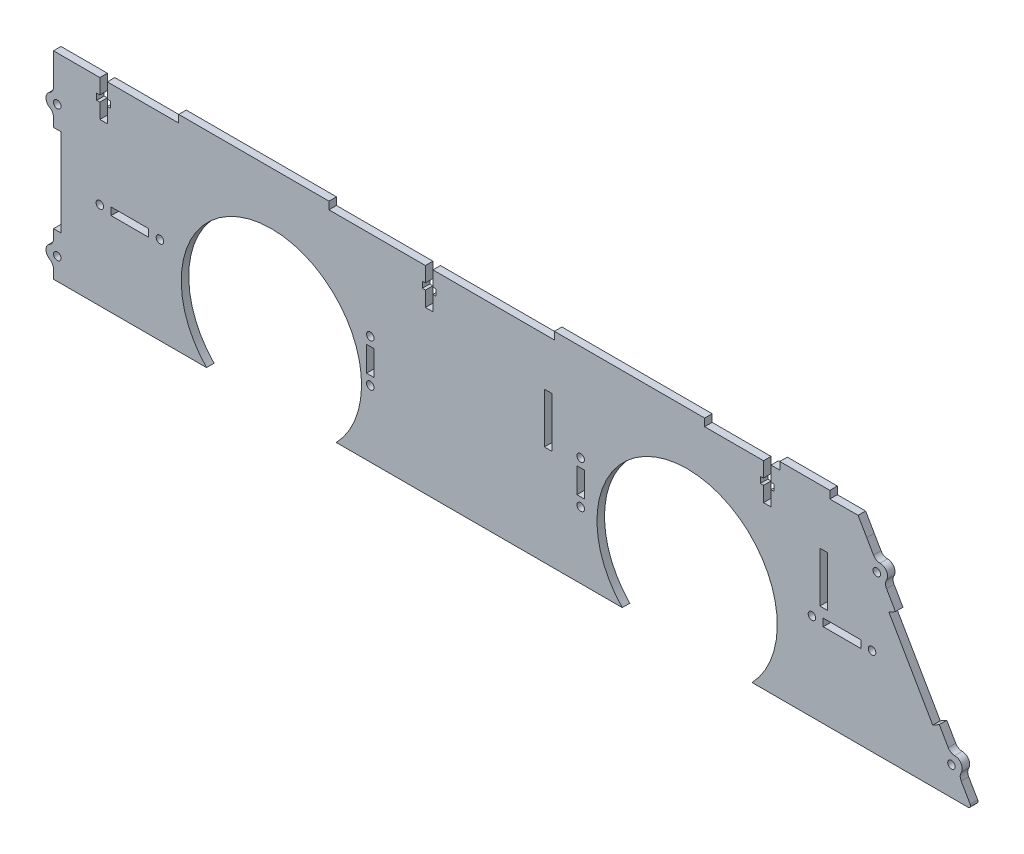
SolidWorks part; units mm, degrees
ref_plane "Спереди" through (0, 0, 0) normal (0, 0, 1) x (1, 0, 0)
ref_plane "Сверху" through (0, 0, 0) normal (0, 1, 0) x (1, 0, 0)
ref_plane "Справа" through (0, 0, 0) normal (1, 0, 0) x (0, 0, -1)
sketch "Эскиз1" plane through (0, 0, 0) normal (0, 0, 1) x (1, 0, 0)
  line L5 (-42.1466, 73) -> (0, 0)
  line L6 (-366.8766, 73) -> (-42.1466, 73)
  line L7 (-366.8766, 0) -> (-366.8766, 73)
  line L8 (0, 0) -> (-366.8766, 0)
  dimension "D1" = 60
  dimension "D2" = 73
  dimension "D3" = 324.73
  dimension "D4" = 84.2931
extrude "Бобышка-Вытянуть1" add sketch "Эскиз1" along normal blind 3
sketch "Эскиз2" plane through (0, 0, 3) normal (0, 0, 1) x (1, 0, 0)
  line L0 (-366.8766, 73) -> (-366.8766, 0) construction
  line L1 (-366.8766, 52.5) -> (-363.8766, 52.5)
  line L2 (-366.8766, 52.5) -> (-366.8766, 17.5)
  line L3 (-366.8766, 17.5) -> (-363.8766, 17.5)
  line L4 (-363.8766, 52.5) -> (-363.8766, 17.5)
  point P6 (-366.8766, 35)
  dimension "D1" = 35
  dimension "D2" = 3
  dimension "D3" = 35
extrude "Вырез-Вытянуть1" cut sketch "Эскиз2" against normal blind 3
sketch "Эскиз3" plane through (0, 0, 3) normal (0, 0, 1) x (1, 0, 0)
  line L0 (-33.2874, 51.6554) -> (-30.6893, 53.1554)
  line L1 (-33.2874, 51.6554) -> (-15.7874, 21.3446)
  line L2 (-30.6893, 53.1554) -> (-13.1893, 22.8446)
  line L3 (-15.7874, 21.3446) -> (-13.1893, 22.8446)
  line L4 (-45.6107, 73) -> (-3.4641, 0) construction
  line L5 (-42.1466, 73) -> (-366.8766, 73) construction
  line L9 (0, 0) -> (-42.1466, 73) construction
  line L10 (-366.8766, 0) -> (0, 0) construction
  line L11 (0, 0) -> (-42.1466, 73) construction
  point P12 (-24.5374, 36.5)
  point P13 (-24.5374, 36.5)
  dimension "D1" = 35
  dimension "D2" = 3
extrude "Вырез-Вытянуть2" cut sketch "Эскиз3" against normal blind 3
sketch "Эскиз4" plane through (0, 0, 3) normal (0, 0, 1) x (1, 0, 0)
  line L0 (-366.8766, 0) -> (0, 0) construction
  line L1 (-241.8766, 40) -> (-238.8766, 40)
  line L2 (-241.8766, 40) -> (-241.8766, 30)
  line L3 (-241.8766, 30) -> (-238.8766, 30)
  line L4 (-238.8766, 40) -> (-238.8766, 30)
  line L5 (-241.8766, 40) -> (-238.8766, 30) construction
  line L6 (-241.8766, 30) -> (-238.8766, 40) construction
  line L7 (-157.8766, 40) -> (-154.8766, 40)
  line L8 (-157.8766, 40) -> (-157.8766, 30)
  line L9 (-157.8766, 30) -> (-154.8766, 30)
  line L10 (-154.8766, 40) -> (-154.8766, 30)
  line L11 (-157.8766, 40) -> (-154.8766, 30) construction
  line L12 (-157.8766, 30) -> (-154.8766, 40) construction
  point P0 (-240.3766, 35)
  point P5 (-156.3766, 35)
  dimension "D1" = 3
  dimension "D2" = 10
  dimension "D3" = 84
  dimension "D4" = 123.5
  dimension "D5" = 35
extrude "Вырез-Вытянуть3" cut sketch "Эскиз4" against normal blind 3
sketch "Эскиз5" plane through (0, 0, 3) normal (0, 0, 1) x (1, 0, 0)
  line L1 (-343.8766, 36.5) -> (-328.8766, 36.5)
  line L2 (-343.8766, 36.5) -> (-343.8766, 33.5)
  line L3 (-343.8766, 33.5) -> (-328.8766, 33.5)
  line L4 (-328.8766, 36.5) -> (-328.8766, 33.5)
  line L5 (-343.8766, 36.5) -> (-328.8766, 33.5) construction
  line L6 (-343.8766, 33.5) -> (-328.8766, 36.5) construction
  line L7 (-59.5366, 36.5) -> (-44.5366, 36.5)
  line L8 (-59.5366, 36.5) -> (-59.5366, 33.5)
  line L9 (-59.5366, 33.5) -> (-44.5366, 33.5)
  line L10 (-44.5366, 36.5) -> (-44.5366, 33.5)
  line L11 (-59.5366, 36.5) -> (-44.5366, 33.5) construction
  line L12 (-59.5366, 33.5) -> (-44.5366, 36.5) construction
  point P0 (-336.3766, 35)
  point P5 (-52.0366, 35)
  dimension "D1" = 15
  dimension "D2" = 3
  dimension "D3" = 27.5
  dimension "D4" = 284.34
  dimension "D5" = 35
extrude "Вырез-Вытянуть4" cut sketch "Эскиз5" against normal blind 3
sketch "Эскиз6" plane through (0, 73, 0) normal (0, 1, 0) x (1, 0, 0)
  line L0 (-42.1466, -3) -> (-366.8766, -3) construction
  line L1 (-366.8766, 0) -> (-42.1466, 0)
  line L2 (-366.8766, 0) -> (-366.8766, -3)
  line L3 (-366.8766, -3) -> (-42.1466, -3)
  line L4 (-42.1466, 0) -> (-42.1466, -3)
extrude "Бобышка-Вытянуть2" add sketch "Эскиз6" along normal blind 6
sketch "Эскиз7" plane through (0, 0, 3) normal (0, 0, 1) x (1, 0, 0)
  line L0 (-366.8766, 17.5) -> (-366.8766, 0) construction
  line L1 (-363.8766, 35) -> (-385.1167, 35) construction
  line L2 (-363.8766, 17.5) -> (-363.8766, 52.5) construction
  circle A0 centre (-365.3766, 8.75) radius 1.5
  circle A1 centre (-365.3766, 61.25) radius 1.5
  point P5 (-366.8766, 8.75)
  dimension "D1" = 3
  dimension "D2" = 1.5
sketch "Эскиз8" plane through (-366.8766, 0, 0) normal (-1, 0, 0) x (0, 0, 1)
  line L0 (0, 17.5) -> (0, 0) construction
  line L1 (0, 8.75) -> (3, 8.75)
  line L2 (0, 8.75) -> (0, 5.75)
  line L3 (0, 5.75) -> (3, 5.75)
  line L4 (3, 8.75) -> (3, 5.75)
  line L5 (3, 17.5) -> (3, 0) construction
  dimension "D1" = 3
revolve "Повернуть1" add sketch "Эскиз8" angle 360 about L1
sketch "Эскиз9" plane through (-366.8766, 0, 0) normal (-1, 0, 0) x (0, 0, 1)
  line L0 (0, 79) -> (0, 52.5) construction
  line L1 (0, 61.25) -> (3, 61.25)
  line L2 (0, 61.25) -> (0, 58.25)
  line L3 (0, 58.25) -> (3, 58.25)
  line L4 (3, 61.25) -> (3, 58.25)
  line L5 (3, 79) -> (3, 52.5) construction
  dimension "D1" = 3
  dimension "D2" = 8.75
revolve "Повернуть2" add sketch "Эскиз9" angle 360 about L1
extrude "Вырез-Вытянуть6" cut sketch "Эскиз7" against normal blind 3
fillet "Скругление1" radius 3 4 edges at (-366.8766, 11.75, 1.5) (-366.8766, 5.75, 1.5) (-366.8766, 58.25, 1.5) (-366.8766, 64.25, 1.5)
sketch "Эскиз14" plane through (0, 0, 3) normal (0, 0, 1) x (1, 0, 0)
  line L0 (-154.8766, 40) -> (-157.8766, 40) construction
  line L1 (-157.8766, 30) -> (-154.8766, 30) construction
  line L2 (-241.8766, 30) -> (-238.8766, 30) construction
  circle A0 centre (-156.3766, 43.5) radius 1.5
  circle A1 centre (-156.3766, 26.5) radius 1.5
  circle A2 centre (-240.3766, 26.5) radius 1.5
  circle A3 centre (-240.3766, 43.5) radius 1.5
  point P11 (-156.3766, 40)
  point P20 (-240.3766, 30)
  dimension "D1" = 3
  dimension "D2" = 3.5
  dimension "D3" = 3.5
extrude "Вырез-Вытянуть9" cut sketch "Эскиз14" against normal blind 3
sketch "Эскиз15" plane through (0, 0, 3) normal (0, 0, 1) x (1, 0, 0)
  line L0 (-59.5366, 36.5) -> (-59.5366, 33.5) construction
  line L1 (-44.5366, 33.5) -> (-44.5366, 36.5) construction
  line L2 (-343.8766, 36.5) -> (-343.8766, 33.5) construction
  line L3 (-328.8766, 33.5) -> (-328.8766, 36.5) construction
  circle A0 centre (-324.3766, 35) radius 1.5
  circle A1 centre (-348.3766, 35) radius 1.5
  circle A2 centre (-64.0366, 35) radius 1.5
  circle A3 centre (-40.0366, 35) radius 1.5
  point P16 (-59.5366, 35)
  dimension "D1" = 3
  dimension "D2" = 4.5
  dimension "D3" = 4.5
  dimension "D4" = 4.5
  dimension "D5" = 4.5
extrude "Вырез-Вытянуть10" cut sketch "Эскиз15" against normal blind 3
sketch "Эскиз16" plane through (0, 0, 0) normal (0.866, 0.5, 0) x (0, 0, -1)
  line L0 (-3, 0) -> (-3, 26.3786) construction
  line L1 (-3, 11.0586) -> (0, 11.0586)
  line L2 (-3, 11.0586) -> (-3, 14.0586)
  line L3 (-3, 14.0586) -> (0, 14.0586)
  line L4 (0, 11.0586) -> (0, 14.0586)
  line L5 (0, 0) -> (0, 26.3786) construction
  dimension "D1" = 3
  dimension "D2" = 12.32
revolve "Повернуть3" add sketch "Эскиз16" angle 360 about L3
sketch "Эскиз17" plane through (0, 0, 0) normal (0.866, 0.5, 0) x (0, 0, -1)
  line L0 (-3, 61.3786) -> (-3, 84.2931) construction
  line L1 (-3, 73.6986) -> (0, 73.6986)
  line L2 (-3, 73.6986) -> (-3, 76.6986)
  line L3 (-3, 76.6986) -> (0, 76.6986)
  line L4 (0, 73.6986) -> (0, 76.6986)
  line L5 (0, 61.3786) -> (0, 84.2931) construction
  dimension "D1" = 3
  dimension "D2" = 12.32
revolve "Повернуть4" add sketch "Эскиз17" angle 360 about L1
sketch "Эскиз18" plane through (0, 0, 3) normal (0, 0, 1) x (1, 0, 0)
  line L1 (-15.7874, 21.3446) -> (-3.4641, 0) construction
  line L2 (0, 0) -> (-5.5293, 9.577) construction
  line L3 (-366.8766, 0) -> (0, 0) construction
  line L5 (-9.6257, 10.6723) -> (-6.0018, 12.7646) construction
  circle A0 centre (-38.15, 63.0777) radius 1.5
  circle A1 centre (-8.3267, 11.4223) radius 1.5
  dimension "D1" = 3
  dimension "D2" = 3
  dimension "D3" = 9.9223
  dimension "D4" = 1.5
  dimension "D5" = 7.4607
extrude "Вырез-Вытянуть11" cut sketch "Эскиз18" against normal blind 3
fillet "Скругление2" radius 3 4 edges at (-38.3493, 66.423, 1.5) (-35.3493, 61.2268, 1.5) (-8.5293, 14.7732, 1.5) (-5.5293, 9.577, 1.5)
chamfer "Фаска1" distance 6 angle 30 1 edges at (-42.1466, 79, 1.5) first distance on face at (-42.1466, 76, 1.5)
sketch "Эскиз19" plane through (0, 0, 3) normal (0, 0, 1) x (1, 0, 0)
  line L0 (-366.8766, 0) -> (0, 0) construction
  line L1 (-363.8766, 17.5) -> (-363.8766, 52.5) construction
  circle A0 centre (-279.8766, 25) radius 36
  circle A1 centre (-113.8766, 25) radius 36
  dimension "D4" = 72
  dimension "D1" = 25
  dimension "D2" = 166
  dimension "D3" = 84
extrude "Вырез-Вытянуть12" cut sketch "Эскиз19" against normal blind 3
sketch "Эскиз24" plane through (0, 79, 0) normal (0, 1, 0) x (1, 0, 0)
  line L0 (-366.8766, -3) -> (-45.6107, -3) construction
  line L1 (-56.8766, -3) -> (-76.8766, -3)
  line L2 (-56.8766, -3) -> (-56.8766, 0)
  line L3 (-56.8766, 0) -> (-76.8766, 0)
  line L4 (-76.8766, -3) -> (-76.8766, 0)
  line L5 (-45.6107, 0) -> (-366.8766, 0) construction
  line L7 (-106.8766, -3) -> (-166.8766, -3)
  line L8 (-106.8766, -3) -> (-106.8766, 0)
  line L9 (-106.8766, 0) -> (-166.8766, 0)
  line L10 (-166.8766, -3) -> (-166.8766, 0)
  line L11 (-316.8766, -3) -> (-256.8766, -3)
  line L12 (-316.8766, -3) -> (-316.8766, 0)
  line L13 (-316.8766, 0) -> (-256.8766, 0)
  line L14 (-256.8766, -3) -> (-256.8766, 0)
  dimension "D1" = 50
  dimension "D2" = 60
  dimension "D3" = 60
  dimension "D4" = 200
  dimension "D5" = 20
  dimension "D6" = 290
extrude "Бобышка-Вытянуть3" add sketch "Эскиз24" along normal blind 3
sketch "Эскиз25" plane through (0, 0, 3) normal (0, 0, 1) x (1, 0, 0)
  line L0 (-348.3766, 79) -> (-348.3766, 73)
  line L1 (-348.3766, 73) -> (-349.6266, 73)
  line L2 (-349.6266, 73) -> (-349.6266, 70.5)
  line L3 (-349.6266, 70.5) -> (-348.3766, 70.5)
  line L4 (-348.3766, 70.5) -> (-348.3766, 64.5)
  line L5 (-348.3766, 64.5) -> (-345.3766, 64.5)
  line L6 (-345.3766, 64.5) -> (-345.3766, 70.5)
  line L7 (-345.3766, 70.5) -> (-344.1266, 70.5)
  line L8 (-344.1266, 70.5) -> (-344.1266, 73)
  line L9 (-344.1266, 73) -> (-345.3766, 73)
  line L10 (-345.3766, 73) -> (-345.3766, 79)
  line L11 (-345.3766, 79) -> (-348.3766, 79)
  line L12 (-218.3766, 79) -> (-218.3766, 73)
  line L13 (-218.3766, 73) -> (-219.6266, 73)
  line L14 (-219.6266, 73) -> (-219.6266, 70.5)
  line L15 (-219.6266, 70.5) -> (-218.3766, 70.5)
  line L16 (-218.3766, 70.5) -> (-218.3766, 64.5)
  line L17 (-218.3766, 64.5) -> (-215.3766, 64.5)
  line L18 (-215.3766, 64.5) -> (-215.3766, 70.5)
  line L19 (-215.3766, 70.5) -> (-214.1266, 70.5)
  line L20 (-214.1266, 70.5) -> (-214.1266, 73)
  line L21 (-214.1266, 73) -> (-215.3766, 73)
  line L22 (-215.3766, 73) -> (-215.3766, 79)
  line L23 (-215.3766, 79) -> (-218.3766, 79)
  line L24 (-83.3766, 79) -> (-83.3766, 73)
  line L25 (-83.3766, 73) -> (-84.6266, 73)
  line L26 (-84.6266, 73) -> (-84.6266, 70.5)
  line L27 (-84.6266, 70.5) -> (-83.3766, 70.5)
  line L28 (-83.3766, 70.5) -> (-83.3766, 64.5)
  line L29 (-83.3766, 64.5) -> (-80.3766, 64.5)
  line L30 (-80.3766, 64.5) -> (-80.3766, 70.5)
  line L31 (-80.3766, 70.5) -> (-79.1266, 70.5)
  line L32 (-79.1266, 70.5) -> (-79.1266, 73)
  line L33 (-79.1266, 73) -> (-80.3766, 73)
  line L34 (-80.3766, 73) -> (-80.3766, 79)
  line L35 (-80.3766, 79) -> (-83.3766, 79)
  line L36 (-366.8766, 79) -> (-316.8766, 79) construction
  line L37 (-256.8766, 79) -> (-166.8766, 79) construction
  line L38 (-106.8766, 79) -> (-76.8766, 79) construction
  point P42 (-346.8766, 79)
  point P47 (-216.8766, 79)
  point P54 (-81.8766, 79)
  dimension "D1" = 6
  dimension "D2" = 3
  dimension "D3" = 2.5
  dimension "D4" = 5.5
  dimension "D5" = 6
  dimension "D6" = 3
  dimension "D7" = 2.5
  dimension "D8" = 5.5
  dimension "D9" = 6
  dimension "D10" = 3
  dimension "D11" = 2.5
  dimension "D12" = 5.5
  dimension "D13" = 20
  dimension "D14" = 150
  dimension "D15" = 285
extrude "Вырез-Вытянуть13" cut sketch "Эскиз25" against normal blind 3
fillet "Скругление3" radius 1 1 edges at (0, 0, 1.5)
sketch "Эскиз26" plane through (0, 0, 3) normal (0, 0, 1) x (1, 0, 0)
  line L0 (-253.9729, 0) -> (-139.7802, 0) construction
  line L1 (-170.8766, 60) -> (-167.8766, 60)
  line L2 (-170.8766, 60) -> (-170.8766, 40)
  line L3 (-170.8766, 40) -> (-167.8766, 40)
  line L4 (-167.8766, 60) -> (-167.8766, 40)
  line L5 (-60.8766, 60) -> (-57.8766, 60)
  line L6 (-60.8766, 60) -> (-60.8766, 40)
  line L7 (-60.8766, 40) -> (-57.8766, 40)
  line L8 (-57.8766, 60) -> (-57.8766, 40)
  line L9 (-157.8766, 40) -> (-157.8766, 30) construction
  point P8 (0, 0)
  dimension "D1" = 3
  dimension "D2" = 20
  dimension "D3" = 40
  dimension "D4" = 110
  dimension "D5" = 10
  dimension "D6" = 196
extrude "Вырез-Вытянуть14" cut sketch "Эскиз26" against normal blind 3
